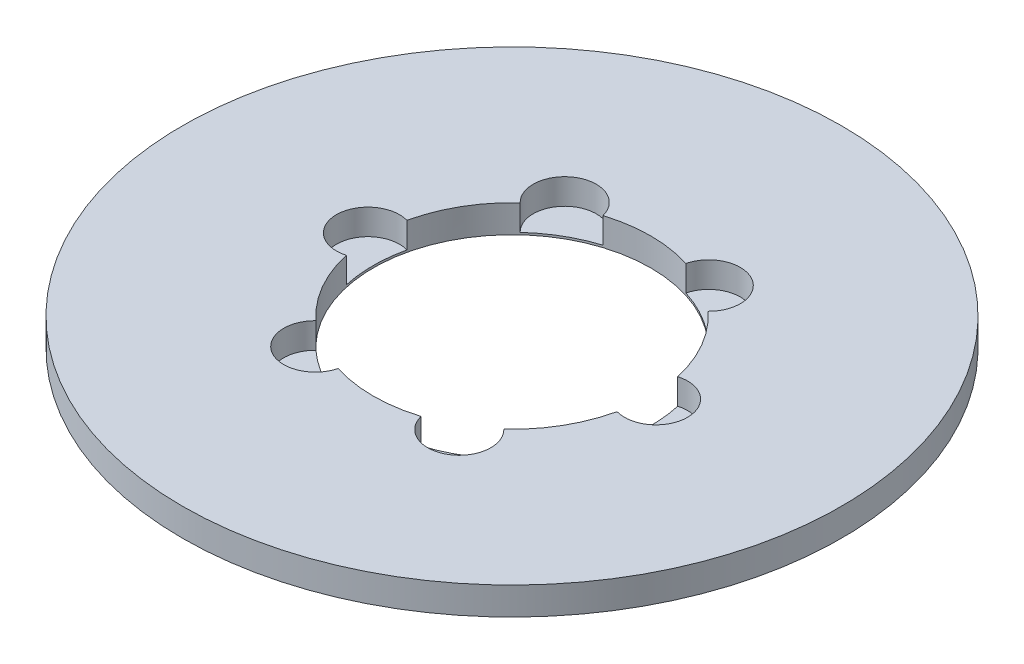
SolidWorks part; units mm, degrees
ref_plane "Front Plane" through (0, 0, 0) normal (0, 0, 1) x (1, 0, 0)
ref_plane "Top Plane" through (0, 0, 0) normal (0, 1, 0) x (1, 0, 0)
ref_plane "Right Plane" through (0, 0, 0) normal (1, 0, 0) x (0, 0, -1)
sketch "Sketch1" plane through (0, 0, 0) normal (0, 1, 0) x (1, 0, 0)
  circle A0 centre (0, 0) radius 95
  dimension "FLANGE_OD" = 190
extrude "Boss-Extrude1" add sketch "Sketch1" along normal blind 8
sketch "Sketch2" plane through (0, 0, 0) normal (0, 1, 0) x (1, 0, 0)
  circle A0 centre (0, 0) radius 40
  dimension "BORE_D" = 80
extrude "Cut-Extrude1" cut sketch "Sketch2" along normal through all
sketch "Sketch3" plane through (0, 8, 0) normal (0, 1, 0) x (1, 0, 0)
  circle A0 centre (0, 0) radius 41.5189 construction
  circle A1 centre (-41.5189, 0) radius 9.0873
  dimension "BOLT_D" = 18.1746
  dimension "BOLT_PCD" = 83.0378
extrude "Cut-Extrude2" cut sketch "Sketch3" against normal blind 7.3885
pattern_circular "CirPattern1" count 6 over 360 about axis through (0, 0, 0) along (0, 1, 0) of "Cut-Extrude2"
